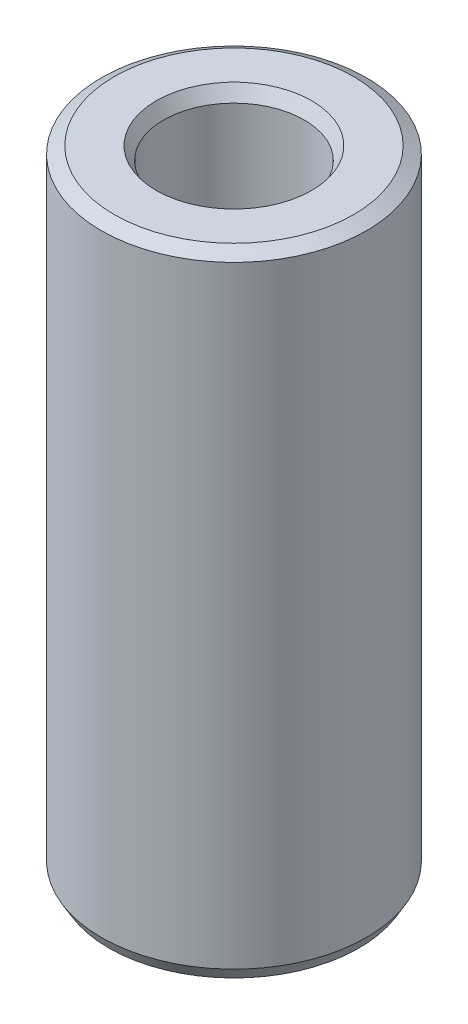
SolidWorks part; units mm, degrees
ref_plane "Front Plane" through (0, 0, 0) normal (0, 0, 1) x (1, 0, 0)
ref_plane "Top Plane" through (0, 0, 0) normal (0, 1, 0) x (1, 0, 0)
ref_plane "Right Plane" through (0, 0, 0) normal (1, 0, 0) x (0, 0, -1)
sketch "Sketch1" plane through (0, 0, 0) normal (0, 1, 0) x (1, 0, 0)
  circle A0 centre (0, 0) radius 35
  dimension "SLEEVE_OD" = 70
extrude "Boss-Extrude1" add sketch "Sketch1" along normal blind 167.0135
sketch "Sketch2" plane through (0, 0, 0) normal (0, 1, 0) x (1, 0, 0)
  circle A0 centre (0, 0) radius 18.5639
  dimension "BORE_D" = 37.1279
extrude "Cut-Extrude1" cut sketch "Sketch2" along normal through all
chamfer "Chamfer1" distance 1.9665 angle 60 4 edges at (0, 167.0135, 18.5639) (0, 0, 18.5639) (0, 0, 35) (0, 167.0135, 35) first distance on face at (0, 167.0135, 18.5639) first distance on face at (0, 0, 18.5639) first distance on face at (0, 167.0135, 35)
